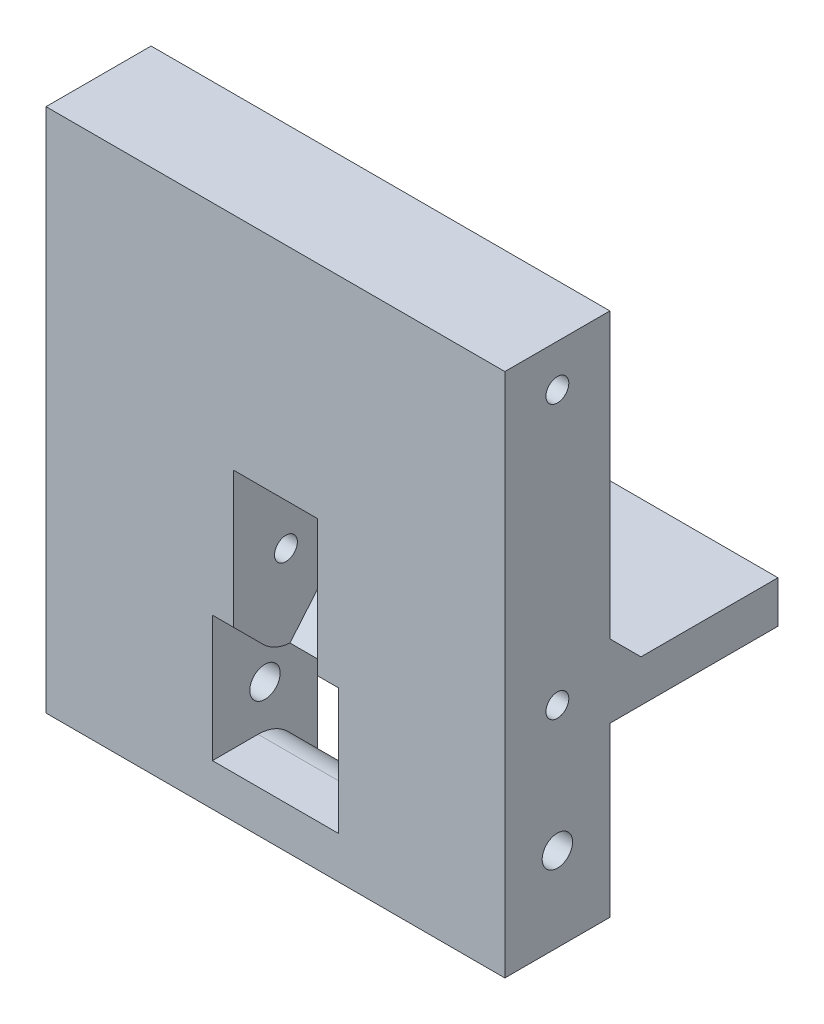
SolidWorks part; units mm, degrees
material "ABS"
ref_plane "Front Plane" through (0, 0, 0) normal (0, 0, 1) x (1, 0, 0)
ref_plane "Top Plane" through (0, 0, 0) normal (0, 1, 0) x (1, 0, 0)
ref_plane "Right Plane" through (0, 0, 0) normal (1, 0, 0) x (0, 0, -1)
sketch "Sketch2" plane through (-62.0532, 0, 0) normal (-1, 0, 0) x (0, 0, 1)
  line L1 (9.2122, 119.5977) -> (25.0872, 119.5977)
  line L2 (9.2122, 119.5977) -> (9.2122, 40.2227)
  line L3 (9.2122, 40.2227) -> (25.0872, 40.2227)
  line L4 (9.2122, 65.6227) -> (-92.3878, 65.6227)
  line L5 (-92.3878, 65.6227) -> (-92.3878, 59.2727)
  line L6 (-92.3878, 59.2727) -> (9.2122, 59.2727)
  line L7 (9.2122, 59.2727) -> (9.2122, 65.6227)
  line L8 (9.2122, 65.6227) -> (-92.3878, 65.6227)
  line L9 (-92.3878, 65.6227) -> (-92.3878, 59.2727)
  line L10 (-92.3878, 59.2727) -> (9.2122, 59.2727)
  line L11 (9.2122, 59.2727) -> (9.2122, 65.6227)
  line L12 (25.0872, 119.5977) -> (25.0872, 40.2227)
  line L13 (9.2122, 65.6227) -> (-16.1878, 65.6227)
  line L14 (9.2122, 65.6227) -> (9.2122, 71.9727)
  line L15 (9.2122, 71.9727) -> (-16.1878, 71.9727)
  line L16 (-16.1878, 65.6227) -> (-16.1878, 71.9727)
  line L17 (15.5622, 114.8352) -> (18.7372, 114.8352) construction
  line L18 (15.5622, 114.8352) -> (15.5622, 111.6602) construction
  line L19 (15.5622, 111.6602) -> (18.7372, 111.6602) construction
  line L20 (18.7372, 114.8352) -> (18.7372, 111.6602) construction
  line L21 (15.5622, 114.8352) -> (18.7372, 111.6602) construction
  line L22 (15.5622, 111.6602) -> (18.7372, 114.8352) construction
  line L23 (15.5622, 73.5602) -> (18.7372, 73.5602) construction
  line L24 (15.5622, 73.5602) -> (15.5622, 70.3852) construction
  line L25 (15.5622, 70.3852) -> (18.7372, 70.3852) construction
  line L26 (18.7372, 73.5602) -> (18.7372, 70.3852) construction
  line L27 (15.5622, 73.5602) -> (18.7372, 70.3852) construction
  line L28 (15.5622, 70.3852) -> (18.7372, 73.5602) construction
  circle A0 centre (17.1497, 71.9727) radius 2.3 construction
  circle A1 centre (17.1497, 113.2477) radius 1.7272
  circle A2 centre (17.1497, 71.9727) radius 1.7272
  line M10 (9.2122, 65.6227) -> (-92.3878, 65.6227)
  line M13 (9.2122, 59.2727) -> (9.2122, 65.6227)
  dimension "D5" = 4.6
  dimension "D8" = 3.4544
  dimension "D9" = 7.9375
  dimension "D10" = 3.175
  dimension "D7" = 6.35
  dimension "D15" = 3.4544
  dimension "D2" = 79.375
  dimension "D3" = 19.05
  dimension "D4" = 15.875
  dimension "D6" = 7.9375
  dimension "D11" = 25.4
  dimension "D12" = 6.35
  dimension "D13" = 3.175
  dimension "D14" = 41.275
  dimension "D1" = 0
extrude "Boss-Extrude1" add sketch "Sketch2" against normal blind 69.85 contours L16 L2 L15 M10 | L12 L1 L2 L3 A1 A0 M13 region at (-62.0532, 79.7185, 17.1497) region at (-62.0532, 68.7977, -3.4878)
sketch "Sketch3" plane through (0, 0, 9.2122) normal (0, 0, -1) x (-1, 0, 0)
  line L2 (17.6032, 46.5727) -> (36.6532, 46.5727)
  line L3 (17.6032, 46.5727) -> (17.6032, 59.2727)
  line L4 (62.0532, 40.2227) -> (62.0532, 65.6227)
  line L5 (62.0532, 65.6227) -> (-7.7968, 65.6227)
  line L6 (-7.7968, 65.6227) -> (-7.7968, 40.2227)
  line L7 (-7.7968, 40.2227) -> (62.0532, 40.2227)
  line L8 (62.0532, 40.2227) -> (62.0532, 65.6227)
  line L9 (62.0532, 65.6227) -> (-7.7968, 65.6227)
  line L10 (-7.7968, 65.6227) -> (-7.7968, 40.2227)
  line L11 (-7.7968, 40.2227) -> (62.0532, 40.2227)
  line L12 (17.6032, 59.2727) -> (36.6532, 59.2727)
  line L13 (36.6532, 46.5727) -> (36.6532, 59.2727)
  line L14 (17.6032, 46.5727) -> (36.6532, 59.2727) construction
  line L15 (17.6032, 59.2727) -> (36.6532, 46.5727) construction
  point P6 (27.1282, 40.2227)
  point P7 (27.1282, 52.9227)
  dimension "D2" = 19.05
  dimension "D3" = 12.7
  dimension "D4" = 12.7
  dimension "D1" = 0
extrude "Cut-Extrude1" cut sketch "Sketch3" against normal blind 127 contours L2 L13 L12 L3
sketch "Sketch4" plane through (7.7968, 0, 0) normal (1, 0, 0) x (0, 0, -1)
  line L0 (-9.2122, 40.2227) -> (-25.0872, 40.2227) construction
  line L1 (-25.0872, 52.9227) -> (-17.1497, 52.9227) construction
  line L2 (-25.0872, 52.9227) -> (-25.0872, 59.2727) construction
  line L3 (-25.0872, 59.2727) -> (-17.1497, 59.2727) construction
  line L4 (-17.1497, 52.9227) -> (-17.1497, 59.2727) construction
  line L5 (-25.0872, 46.5727) -> (-9.2122, 46.5727)
  line L7 (-9.2122, 46.5727) -> (-9.2122, 59.2727)
  line L8 (-9.2122, 59.2727) -> (-25.0872, 59.2727)
  line L9 (-25.0872, 59.2727) -> (-25.0872, 46.5727)
  line L10 (-25.0872, 46.5727) -> (-9.2122, 46.5727) construction
  line L12 (-9.2122, 46.5727) -> (-9.2122, 59.2727) construction
  line L13 (-9.2122, 59.2727) -> (-25.0872, 59.2727) construction
  line L14 (-25.0872, 59.2727) -> (-25.0872, 46.5727) construction
  circle A0 centre (-17.1497, 52.9227) radius 2.2951
  dimension "D2" = 4.5901
  dimension "D3" = 12.7
  dimension "D1" = 0
extrude "Cut-Extrude2" cut sketch "Sketch4" against normal blind 127 contours A0
chamfer "Chamfer1" distance 6.35 angle 45 2 edges at (-27.1282, 46.5727, 9.2122) (-27.1282, 59.2727, 25.0872)
fillet "Fillet2" radius 6.35 2 edges at (-27.1282, 46.5727, 15.5622) (-27.1282, 59.2727, 18.7372)
sketch "Sketch8" plane through (-27.1282, 59.2727, 33.483) normal (-1, 0, 0) x (0, 0, 1)
  line L0 (-24.2707, 12.7) -> (-49.6707, 12.7) construction
  line L1 (-24.2707, 12.7) -> (-49.6707, 12.7)
  line L2 (-2.8258, 22.4609) -> (-2.8258, 22.4965)
  line L3 (-15.9276, 35.8951) -> (9.2394, 5.9023)
  line L4 (9.2394, 5.9023) -> (-7.0779, -7.7896)
  line L5 (-7.0779, -7.7896) -> (-20.0855, 7.7123)
  line L6 (-20.0855, 7.7123) -> (-24.2707, 12.7)
  line L7 (-7.0779, -7.7896) -> (-24.2707, 12.7)
  line L8 (-7.0779, -7.7896) -> (-9.0237, -9.4222)
  line L9 (-24.2707, 12.7) -> (-26.2165, 11.0673)
  line L10 (-9.0237, -9.4222) -> (-26.2165, 11.0673)
  line L11 (-26.2165, 11.0673) -> (-27.5864, 12.7)
  circle A0 centre (-30.5207, 23.65) radius 2.4 construction
  circle A1 centre (-30.5207, 23.65) radius 2.4
  circle A2 centre (-30.5207, 23.65) radius 19.05
  dimension "D1" = 38.1
  dimension "D2" = 130
  dimension "D3" = 2.54
extrude "Cut-Extrude3" cut sketch "Sketch8" against normal blind 6.35 and the other way blind 6.35 contours A2 L10 L8 L5 | L10 A2 L6 L9 | L11 L9 L1 | A2 L5 L4 L3 | L6 A2 L1 A1 region at (-27.1282, 71.4285, 7.4584) region at (-27.1282, 72.49, 7.5544) region at (-27.1282, 68.752, 10.2779) region at (-27.1282, 68.3478, 27.4388) region at (-27.1282, 58.4952, 18.8569)
sketch "Sketch10" plane through (0, 0, 9.2122) normal (0, 0, -1) x (-1, 0, 0)
  line L0 (33.4782, 71.9727) -> (62.0532, 71.9727) construction
  line L1 (41.4998, 71.9727) -> (51.0248, 71.9727)
  line L2 (41.4998, 71.9727) -> (41.4998, 76.6717)
  line L3 (41.4998, 76.6717) -> (51.0248, 76.6717)
  line L4 (51.0248, 71.9727) -> (51.0248, 76.6717)
  line L5 (41.4998, 104.6609) -> (51.0248, 104.6609)
  line L6 (41.4998, 104.6609) -> (41.4998, 99.9619)
  line L7 (41.4998, 99.9619) -> (51.0248, 99.9619)
  line L8 (51.0248, 104.6609) -> (51.0248, 99.9619)
  line L9 (62.0532, 119.5977) -> (62.0532, 71.9727) construction
  dimension "D1" = 20.5534
  dimension "D2" = 23.2902
  dimension "D3" = 4.699
  dimension "D4" = 9.525
extrude "Boss-Extrude2" add sketch "Sketch10" along normal blind 12.7
sketch "Sketch12" plane through (-41.4998, 0, 0) normal (1, 0, 0) x (0, 0, -1)
  line L0 (-2.8622, 74.8168) -> (-2.8622, 101.8168) construction
  line L1 (3.4878, 76.6717) -> (3.4878, 99.9619) construction
  line L2 (3.4878, 104.6609) -> (3.4878, 99.9619) construction
  line L3 (3.4878, 99.9619) -> (-9.2122, 99.9619) construction
  circle A0 centre (-2.8622, 101.8168) radius 0.8763
  circle A1 centre (-2.8622, 74.8168) radius 0.8763
  point P11 (3.4878, 88.3168)
  point P12 (-2.8622, 88.3168)
  dimension "D1" = 1.7526
  dimension "D2" = 27
extrude "Cut-Extrude4" cut sketch "Sketch12" against normal through all
chamfer "Chamfer2" distance 4.7752 distance2 12.7 1 edges at (-46.2623, 104.6609, 9.2122) first distance on face at (-33.5063, 85.5177, 9.2122)
chamfer "Chamfer3" distance 4.7015 angle 45 2 edges at (-56.539, 71.9727, 9.2122) (-6.4907, 71.9727, 9.2122)
chamfer "Chamfer4" distance 6.35 distance2 12.7 1 edges at (-51.0248, 104.699, 9.2122) first distance on face at (-30.0026, 89.1675, 9.2122)
sketch "Sketch13" plane through (7.7968, 0, 0) normal (1, 0, 0) x (0, 0, -1)
  line L9 (16.1878, 65.6227) -> (16.1878, 71.9727)
  line L10 (16.1878, 71.9727) -> (-4.5107, 71.9727)
  line L11 (-4.5107, 71.9727) -> (-9.2122, 76.6743)
  line L12 (-9.2122, 76.6743) -> (-9.2122, 119.5977)
  line L13 (-9.2122, 119.5977) -> (-25.0872, 119.5977)
  line L14 (-25.0872, 119.5977) -> (-25.0872, 40.2227)
  line L15 (-25.0872, 40.2227) -> (-9.2122, 40.2227)
  line L16 (-9.2122, 40.2227) -> (-9.2122, 65.6227)
  line L17 (-9.2122, 65.6227) -> (16.1878, 65.6227)
  line L18 (16.1878, 65.6227) -> (16.1878, 71.9727)
  line L19 (16.1878, 71.9727) -> (-4.5107, 71.9727)
  line L20 (-4.5107, 71.9727) -> (-9.2122, 76.6743)
  line L21 (-9.2122, 76.6743) -> (-9.2122, 119.5977)
  line L22 (-9.2122, 119.5977) -> (-25.0872, 119.5977)
  line L23 (-25.0872, 119.5977) -> (-25.0872, 40.2227)
  line L24 (-25.0872, 40.2227) -> (-9.2122, 40.2227)
  line L25 (-9.2122, 40.2227) -> (-9.2122, 65.6227)
  line L26 (-9.2122, 65.6227) -> (16.1878, 65.6227)
  dimension "D1" = 0
extrude "Cut-Extrude5" cut sketch "Sketch13" against normal blind 0.254
sketch "Sketch14" plane through (-62.0532, 0, 0) normal (-1, 0, 0) x (0, 0, 1)
  line L9 (-16.1878, 71.9727) -> (-16.1878, 65.6227)
  line L10 (-16.1878, 65.6227) -> (9.2122, 65.6227)
  line L11 (9.2122, 65.6227) -> (9.2122, 40.2227)
  line L12 (9.2122, 40.2227) -> (25.0872, 40.2227)
  line L13 (25.0872, 40.2227) -> (25.0872, 119.5977)
  line L14 (25.0872, 119.5977) -> (9.2122, 119.5977)
  line L15 (9.2122, 119.5977) -> (9.2122, 76.6743)
  line L16 (9.2122, 76.6743) -> (4.5107, 71.9727)
  line L17 (4.5107, 71.9727) -> (-16.1878, 71.9727)
  line L18 (-16.1878, 71.9727) -> (-16.1878, 65.6227)
  line L19 (-16.1878, 65.6227) -> (9.2122, 65.6227)
  line L20 (9.2122, 65.6227) -> (9.2122, 40.2227)
  line L21 (9.2122, 40.2227) -> (25.0872, 40.2227)
  line L22 (25.0872, 40.2227) -> (25.0872, 119.5977)
  line L23 (25.0872, 119.5977) -> (9.2122, 119.5977)
  line L24 (9.2122, 119.5977) -> (9.2122, 76.6743)
  line L25 (9.2122, 76.6743) -> (4.5107, 71.9727)
  line L26 (4.5107, 71.9727) -> (-16.1878, 71.9727)
  dimension "D1" = 0
extrude "Cut-Extrude6" cut sketch "Sketch14" against normal blind 0.254
